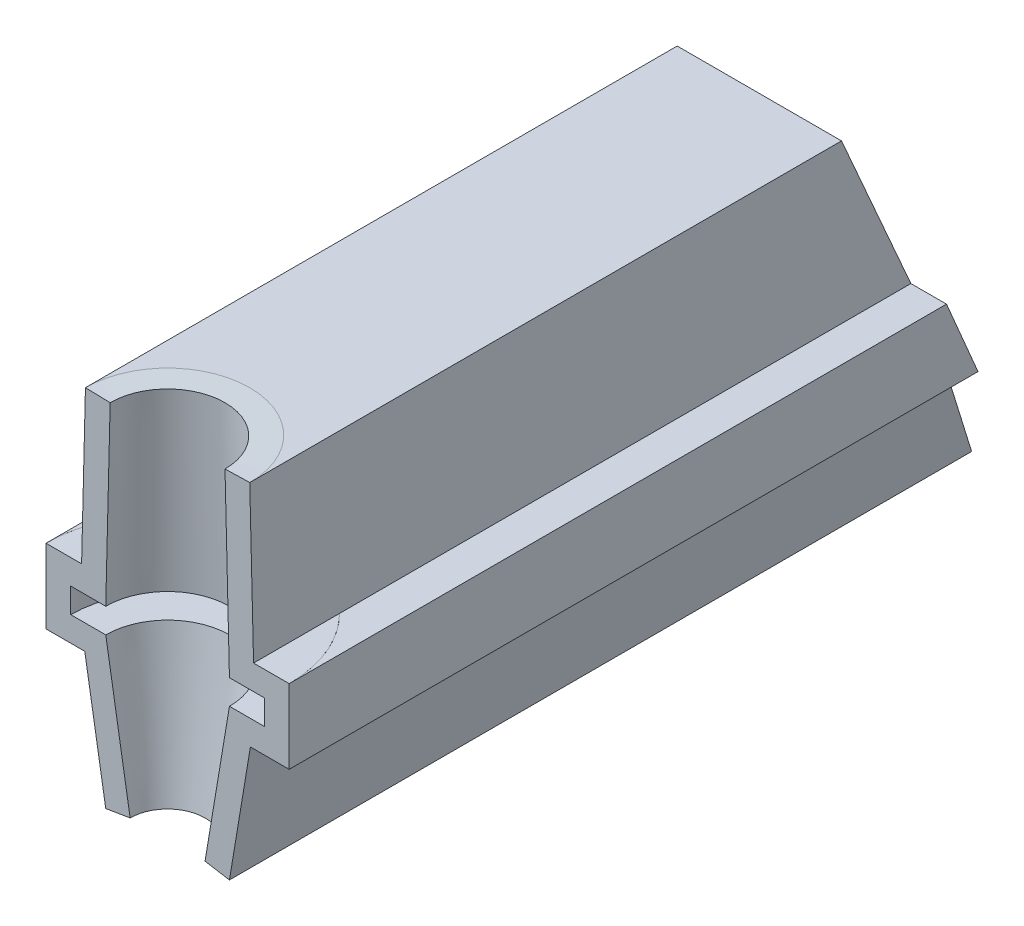
SolidWorks part; units mm, degrees
ref_plane "Front Plane" through (0, 0, 0) normal (0, 0, 1) x (1, 0, 0)
ref_plane "Top Plane" through (0, 0, 0) normal (0, 1, 0) x (1, 0, 0)
ref_plane "Right Plane" through (0, 0, 0) normal (1, 0, 0) x (0, 0, -1)
sketch "Sketch1" plane through (0, 0, 0) normal (0, 0, 1) x (1, 0, 0)
  line L0 (0, 0) -> (0, 27.838) construction
  line L1 (5.0006, -2.7759) -> (6.6943, 7.3858)
  line L2 (3.0279, -2.4471) -> (5, 9.3858)
  line L3 (5, 9.3858) -> (7.8293, 9.3858)
  line L4 (7.8293, 9.3858) -> (7.8293, 11.3858)
  line L5 (7.8293, 11.3858) -> (5, 11.3858)
  line L6 (5, 11.3858) -> (4.6419, 25.8213)
  line L7 (6.6943, 7.3858) -> (9.8293, 7.3858)
  line L8 (9.8293, 7.3858) -> (9.8293, 13.3858)
  line L9 (9.8293, 13.3858) -> (6.951, 13.3858)
  line L10 (6.951, 13.3858) -> (6.6413, 25.8709)
  line L11 (3.0279, -2.4471) -> (5.0006, -2.7759)
  line L12 (4.6419, 25.8213) -> (6.6413, 25.8709)
  line L13 (3.0279, -2.4471) -> (5, 9.3858) construction
  line L14 (4.9758, 12.361) -> (3.0048, 91.806) construction
  dimension "D1" = 2
  dimension "D2" = 2
revolve "Revolve1" add sketch "Sketch1" angle 180 about L0
ref_plane "Plane1" through (0, 2.3465, 4.0642) normal (0, 0.5, 0.866) x (-1, 0, 0)
sketch "Sketch4" plane through (0, 0, 0) normal (0, 0, 1) x (1, 0, 0)
  line L0 (-6.951, 13.3858) -> (-9.8293, 13.3858)
  line L5 (-6.6413, 25.8709) -> (6.6413, 25.8709) construction
  line L6 (6.6413, 25.8709) -> (6.951, 13.3858) construction
  line L7 (6.6943, 7.3858) -> (9.8293, 7.3858)
  line L11 (-6.951, 13.3858) -> (-6.6413, 25.8709) construction
  line L13 (6.6943, 7.3858) -> (5.0006, -2.7759) construction
  line L14 (5.0006, -2.7759) -> (-5.0006, -2.7759) construction
  line L15 (-5.0006, -2.7759) -> (-6.6943, 7.3858) construction
  line L16 (9.8293, 7.3858) -> (9.8293, 13.3858) construction
  line L17 (-9.8293, 7.3858) -> (9.8293, 7.3858) construction
  line L18 (-9.8293, 7.3858) -> (-9.8293, 13.3858) construction
  line L19 (9.8293, 13.3858) -> (-9.8293, 13.3858) construction
  line L20 (-6.6413, 25.8709) -> (6.6413, 25.8709)
  line L21 (6.6413, 25.8709) -> (6.951, 13.3858)
  line L23 (-6.951, 13.3858) -> (-6.6413, 25.8709)
  line L25 (6.6943, 7.3858) -> (5.0006, -2.7759)
  line L26 (5.0006, -2.7759) -> (-5.0006, -2.7759)
  line L27 (-5.0006, -2.7759) -> (-6.6943, 7.3858)
  line L28 (9.8293, 7.3858) -> (9.8293, 13.3858)
  line L29 (-9.8293, 7.3858) -> (-6.6943, 7.3858)
  line L30 (-9.8293, 7.3858) -> (-9.8293, 13.3858)
  line L31 (9.8293, 13.3858) -> (6.951, 13.3858)
extrude "Boss-Extrude3" add sketch "Sketch4" along normal up to body from offset 60 separate body offset against normal yes
sketch "Sketch5" plane through (9.8293, 0, 0) normal (1, 0, 0) x (0, 0, -1)
  line L3 (60, -2.7759) -> (60, 25.8709)
  line L4 (60, 25.8709) -> (47.8402, 25.8709)
  line L5 (47.8402, 25.8709) -> (60, -2.7759)
  dimension "D1" = 23
extrude "Cut-Extrude1" cut sketch "Sketch5" against normal through all
